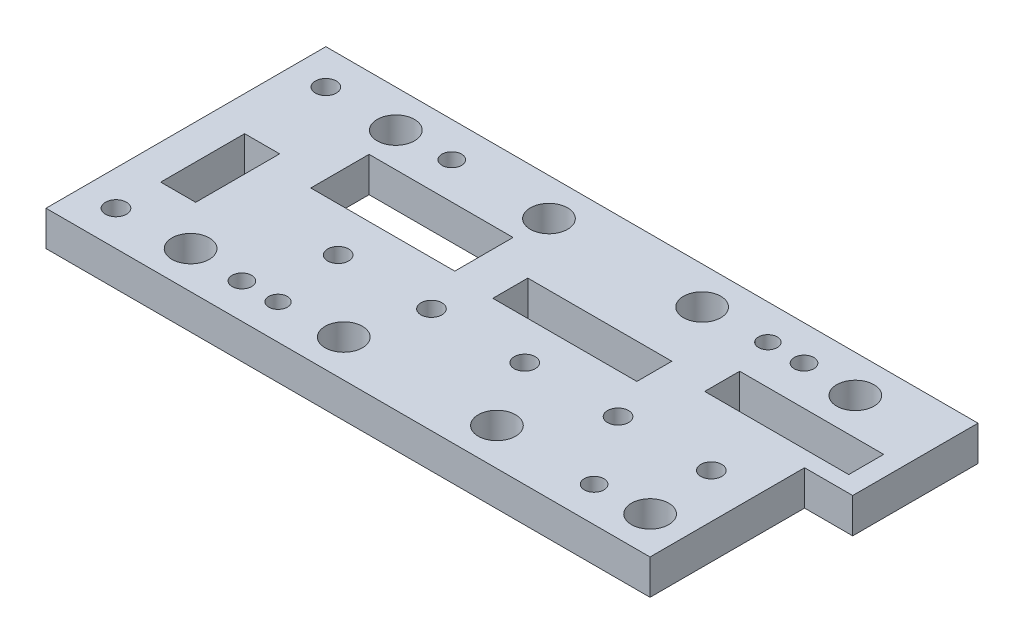
SolidWorks part; units mm, degrees
material "Plain Carbon Steel"
ref_plane "Front Plane" through (0, 0, 0) normal (0, 0, 1) x (1, 0, 0)
ref_plane "Top Plane" through (0, 0, 0) normal (0, 1, 0) x (1, 0, 0)
ref_plane "Right Plane" through (0, 0, 0) normal (1, 0, 0) x (0, 0, -1)
sketch "Sketch1" plane through (0, 0, 0) normal (0, 1, 0) x (1, 0, 0)
  line L0 (-229, 60) -> (-229, -60) construction
  line L1 (-229, -60) -> (0, -60)
  line L2 (-229, -60) -> (-229, 60)
  line L3 (-229, 60) -> (0, 60)
  line L4 (0, -60) -> (0, 60)
  point P4 (0, 0)
  dimension "D1" = 120
extrude "Boss-Extrude1" add sketch "Sketch1" along normal mid plane 15
ref_plane "Plane2" through (-114.5, 0, 0) normal (1, 0, 0) x (0, 0, -1)
sketch "Sketch4" plane through (0, 7.5, 0) normal (0, 1, 0) x (1, 0, 0)
  line L1 (0, 60) -> (20.6325, 60)
  line L2 (0, 60) -> (0, 6.27)
  line L3 (0, 6.27) -> (20.6325, 6.27)
  line L4 (20.6325, 60) -> (20.6325, 6.27)
extrude "Boss-Extrude2" add sketch "Sketch4" against normal up to surface (15 mm away) up to face at (-114.5, -7.5, 0)
sketch "Sketch5" plane through (0, 7.5, 0) normal (0, 1, 0) x (1, 0, 0)
  line L1 (-129.75, 17.3524) -> (-68, 17.3524)
  line L2 (-129.75, 17.3524) -> (-129.75, 2.3524)
  line L3 (-129.75, 2.3524) -> (-68, 2.3524)
  line L4 (-68, 17.3524) -> (-68, 2.3524)
  line L5 (-49.75, 28.191) -> (12, 28.191)
  line L6 (-49.75, 28.191) -> (-49.75, 13.191)
  line L7 (-49.75, 13.191) -> (12, 13.191)
  line L8 (12, 28.191) -> (12, 13.191)
  line L9 (-209.75, 29.28) -> (-148, 29.28)
  line L10 (-209.75, 29.28) -> (-209.75, 4.28)
  line L11 (-209.75, 4.28) -> (-148, 4.28)
  line L12 (-148, 29.28) -> (-148, 4.28)
extrude "Cut-Extrude1" cut sketch "Sketch5" against normal up to next
sketch "Sketch8" plane through (0, 7.5, 0) normal (0, 1, 0) x (1, 0, 0)
  line L3 (-11, 0) -> (11, 0) construction
  line L4 (-114.5, -11) -> (-114.5, 11) construction
  circle A0 centre (-213, 44) radius 8
  dimension "D1" = 16
  dimension "D2" = 44
  dimension "D3" = 98.5
extrude "Cut-Extrude4" cut sketch "Sketch8" against normal up to next
pattern_linear "LPattern2" count 4 spacing 65.677 along (1, 0, 0) count 2 spacing 88 along (0, 0, 1) of "Cut-Extrude4"
hole_wizard "Ø9.0 (9) Diameter Hole1" positions "Sketch11" profile "Sketch10" hole size "Ø9.0" standard "ISO" end condition through all
sketch "Sketch11" plane through (0, 7.5, 0) normal (0, 1, 0) x (1, 0, 0)
  point P0 (-179, -14.72)
  point P3 (-139, -14.72)
  point P6 (-99, -14.72)
  point P9 (-59, -14.72)
  point P12 (-19, -14.72)
sketch "Sketch10" plane through (-179, 7.5, 14.72) normal (1, 0, 0) x (0, 0, 1)
  line L0 (0, 0) -> (0, 15)
  line L1 (0, 15) -> (4.5, 15)
  line L2 (4.5, 15) -> (4.5, 0)
  line L5 (4.5, 0) -> (0, 0)
  line L11 (0, -6.35) -> (0, 107.95) construction
  dimension "Thru Hole Dia." = 9
  dimension "Thru Hole Depth" = 15
hole_wizard "CBORE for M8 Hex Socket Head Cap Screw1" positions "Sketch14" profile "Sketch13" counterbore size "M8" standard "ISO" end condition through all
sketch "Sketch14" plane through (0, -7.5, 0) normal (0, -1, 0) x (-1, 0, 0)
  line L0 (-20.6325, 60) -> (229, 60) construction
  line L1 (229, -60) -> (0, -60) construction
  circle A0 centre (15.969, 44) radius 8 construction
  circle A1 centre (213, 44) radius 8 construction
  point P0 (38.969, 45)
  point P2 (190, 45)
  point P4 (190, -45)
  point P6 (38.969, -45)
  dimension "D1" = 15
  dimension "D2" = 15
  dimension "D3" = 15
  dimension "D4" = 15
sketch "Sketch13" plane through (-38.969, -7.5, -45) normal (1, 0, 0) x (0, 0, -1)
  line L0 (0, 0) -> (0, 15)
  line L1 (0, 15) -> (4.2, 15)
  line L3 (4.2, 15) -> (4.2, 8.6)
  line L4 (4.2, 8.6) -> (7.5, 8.6)
  line L5 (7.5, 8.6) -> (7.5, 0)
  line L7 (7.5, 0) -> (0, 0)
  line L11 (0, -6.35) -> (0, 107.95) construction
  dimension "Thru Hole Dia." = 8.4
  dimension "Thru Hole Depth" = 15
  dimension "C'Bore Dia." = 15
  dimension "C'Bore Depth" = 8.6
hole_wizard "Ø8.0mm Dowel Hole1" positions "Sketch17" profile "Sketch16" hole size "Ø8.0" standard "ISO" end condition through all
sketch "Sketch17" plane through (0, -7.5, 0) normal (0, -1, 0) x (-1, 0, 0)
  line L0 (-20.6325, 60) -> (229, 60) construction
  line L1 (229, -60) -> (0, -60) construction
  circle A0 centre (190, -45) radius 7.5 construction
  circle A1 centre (38.969, 45) radius 7.5 construction
  point P0 (174.5, -45)
  point P2 (54.469, 45)
  dimension "D1" = 8
  dimension "D2" = 8
  dimension "D3" = 15
  dimension "D4" = 15
sketch "Sketch16" plane through (-174.5, -7.5, 45) normal (1, 0, 0) x (0, 0, -1)
  line L0 (0, 0) -> (0, 15)
  line L1 (0, 15) -> (4, 15)
  line L2 (4, 15) -> (4, 0)
  line L5 (4, 0) -> (0, 0)
  line L11 (0, -6.35) -> (0, 107.95) construction
  dimension "Thru Hole Dia." = 8
  dimension "Thru Hole Depth" = 15
sketch "Sketch18" plane through (-229, 0, 0) normal (-1, 0, 0) x (0, 0, 1)
  line L4 (-60, -7.5) -> (60, -7.5)
  line L5 (60, -7.5) -> (60, 7.5)
  line L6 (60, 7.5) -> (-60, 7.5)
  line L7 (-60, 7.5) -> (-60, -7.5)
  line L8 (-60, -7.5) -> (60, -7.5)
  line L9 (60, -7.5) -> (60, 7.5)
  line L10 (60, 7.5) -> (-60, 7.5)
  line L11 (-60, 7.5) -> (-60, -7.5)
  dimension "D1" = 0
extrude "Boss-Extrude3" add sketch "Sketch18" along normal blind 30
sketch "Sketch19" plane through (0, 7.5, 0) normal (0, 1, 0) x (1, 0, 0)
  line L4 (-229.1, -25.72) -> (-229.1, 10.28)
  line L5 (-229.1, 10.28) -> (-244.1, 10.28)
  line L6 (-244.1, 10.28) -> (-244.1, -25.72)
  line L7 (-244.1, -25.72) -> (-229.1, -25.72)
  line L8 (-229.1, -25.72) -> (-229.1, 10.28)
  line L9 (-229.1, 10.28) -> (-244.1, 10.28)
  line L10 (-244.1, 10.28) -> (-244.1, -25.72)
  line L11 (-244.1, -25.72) -> (-229.1, -25.72)
  dimension "D1" = 0
extrude "Cut-Extrude5" cut sketch "Sketch19" against normal up to next
hole_wizard "CBORE for M8 Hex Socket Head Cap Screw2" positions "Sketch22" profile "Sketch21" counterbore size "M8" standard "ISO" end condition through all
sketch "Sketch22" plane through (0, -7.5, 0) normal (0, -1, 0) x (-1, 0, 0)
  line L0 (190, 45) -> (244, 45) construction
  line L3 (259, 60) -> (259, -60) construction
  line L4 (190, -45) -> (244, -45) construction
  point P0 (244, 45)
  point P2 (244, -45)
  dimension "D1" = 15
sketch "Sketch21" plane through (-244, -7.5, -45) normal (1, 0, 0) x (0, 0, -1)
  line L0 (0, 0) -> (0, 15)
  line L1 (0, 15) -> (4.5, 15)
  line L3 (4.5, 15) -> (4.5, 8.6)
  line L4 (4.5, 8.6) -> (7.5, 8.6)
  line L5 (7.5, 8.6) -> (7.5, 0)
  line L7 (7.5, 0) -> (0, 0)
  line L11 (0, -6.35) -> (0, 107.95) construction
  dimension "Thru Hole Dia." = 9
  dimension "Thru Hole Depth" = 15
  dimension "C'Bore Dia." = 15
  dimension "C'Bore Depth" = 8.6
